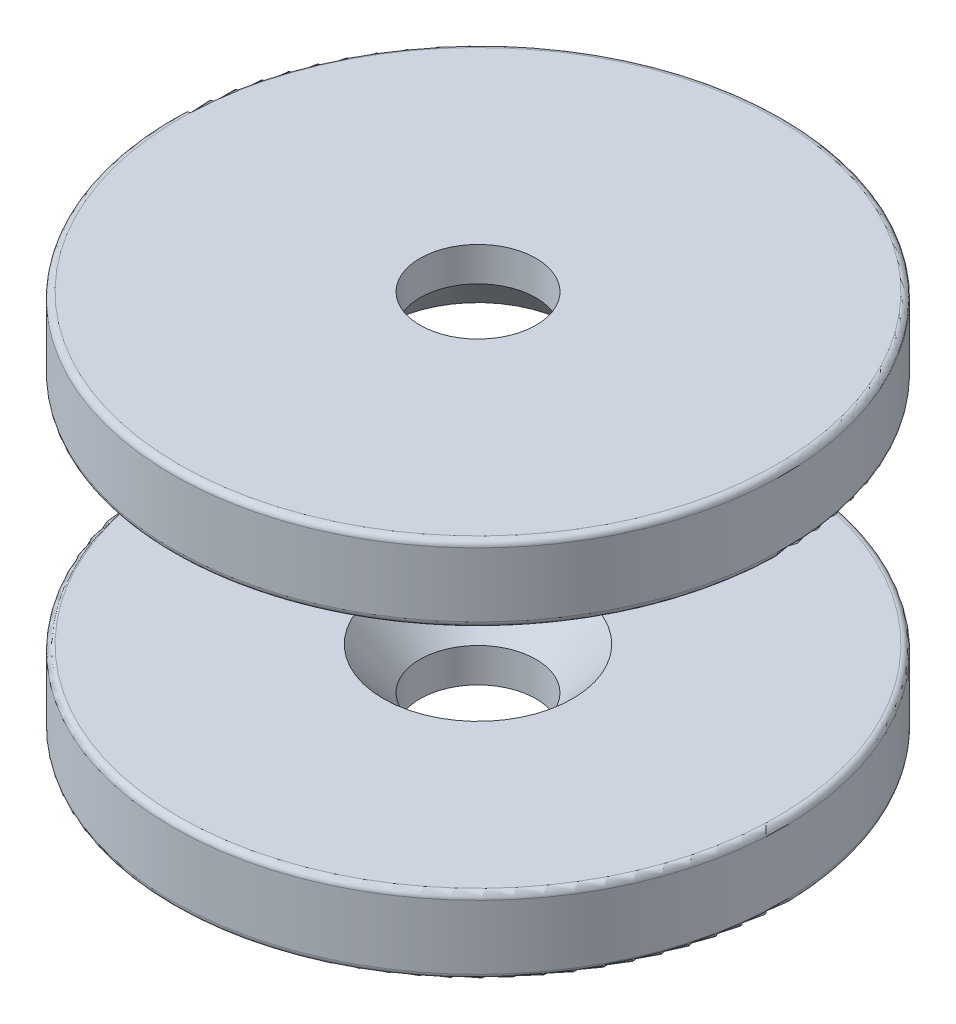
SolidWorks part; units mm, degrees
ref_plane "Front Plane" through (0, 0, 0) normal (0, 0, 1) x (1, 0, 0)
ref_plane "Top Plane" through (0, 0, 0) normal (0, 1, 0) x (1, 0, 0)
ref_plane "Right Plane" through (0, 0, 0) normal (1, 0, 0) x (0, 0, -1)
sketch "Sketch1" plane through (0, 0, 0) normal (0, 1, 0) x (1, 0, 0)
  circle A0 centre (0, 0) radius 12.7
  circle A1 centre (0, 0) radius 2.413
  dimension "D1" = 4.826
  dimension "OD" = 25.4
extrude "Boss-Extrude1" add sketch "Sketch1" along normal mid plane 3.175
fillet "Fillet1" radius 0.254 2 edges at (0, -1.5875, 12.7) (0, 1.5875, 12.7)
sketch "Sketch2" plane through (0, 1.5875, 0) normal (0, 1, 0) x (1, 0, 0)
  circle A0 centre (0, 0) radius 3.937
  dimension "D1" = 7.874
extrude "Cut-Extrude1" cut sketch "Sketch2" against normal through all draft 41
move or copy body "Body-Move/Copy1" bodies to move or copy 103 copy yes number of copies 1 rotation origin (0, 0, 0) rotation axis (1, 0, 0) rotation angle 180
move or copy body "Body-Move/Copy2" bodies to move or copy 102 copy no translate (0, 12.7, 0)
ref_axis "Center Axis 1" through (0, 15.0813, 0) along (0, -1, 0)
ref_plane "Contact Plane 1" through (0, -1.5875, 0) normal (0, -1, 0) x (-1, 0, 0)
ref_plane "Contact Plane 2" through (0, 14.2875, 0) normal (0, 1, 0) x (1, 0, 0)
